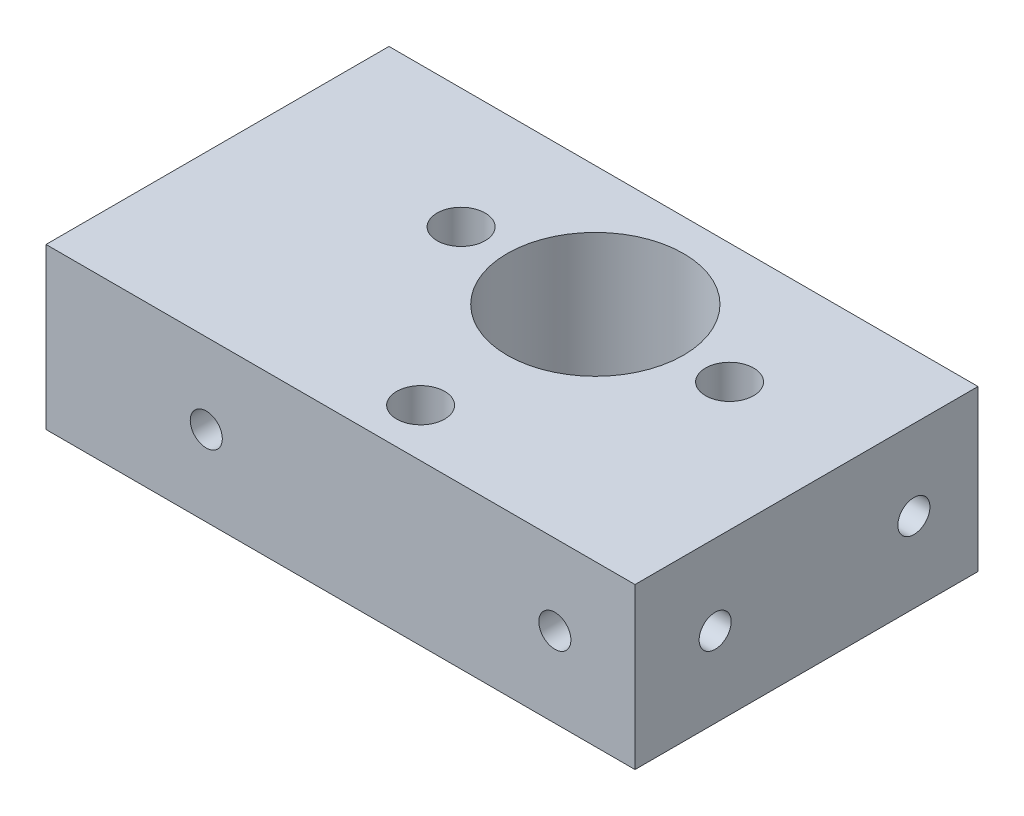
SolidWorks part; units mm, degrees
ref_plane "前视基准面" through (0, 0, 0) normal (0, 0, 1) x (1, 0, 0)
ref_plane "上视基准面" through (0, 0, 0) normal (0, 1, 0) x (1, 0, 0)
ref_plane "右视基准面" through (0, 0, 0) normal (1, 0, 0) x (0, 0, -1)
other "Configuration Table"
sketch "草图1" plane through (0, 0, 0) normal (0, 1, 0) x (1, 0, 0)
  line L0 (-8.375, 0) -> (8.375, 0)
  line L33 (-16.375, -7.5) -> (16.375, -7.5)
  line L34 (-16.375, -7.5) -> (-16.375, 7.5)
  line L35 (-16.375, 7.5) -> (16.375, 7.5)
  line L36 (16.375, -7.5) -> (16.375, 7.5)
  line L37 (-16.375, -7.5) -> (16.375, 7.5) construction
  line L38 (-16.375, 7.5) -> (16.375, -7.5) construction
  line L44 (16.375, -7.5) -> (-16.375, -7.5)
  line L45 (16.375, -7.5) -> (16.375, -13.9)
  line L46 (16.375, -13.9) -> (-16.375, -13.9)
  line L47 (-16.375, -7.5) -> (-16.375, -13.9)
  line L48 (-20.375, 7.5) -> (-16.375, 7.5)
  line L49 (-20.375, 7.5) -> (-20.375, -13.9)
  line L50 (-20.375, -13.9) -> (-16.375, -13.9)
  line L51 (-16.375, 7.5) -> (-16.375, -13.9)
  circle A0 centre (0, 0) radius 5.5
  circle A1 centre (-8.375, 0) radius 2.25
  circle A2 centre (-8.375, 0) radius 1.5
  circle A3 centre (8.375, 0) radius 2.25
  circle A4 centre (8.375, 0) radius 1.5
  circle A5 centre (0, -10.9) radius 1.5
  circle A6 centre (0, -10.9) radius 2.25
  point P0 (-90.6464, 22.0667)
  point P11 (0, 0)
  dimension "D1" = 11
  dimension "D2" = 15
  dimension "D3" = 16.75
  dimension "D4" = 3
  dimension "D5" = 4.5
  dimension "D6" = 8
  dimension "D7" = 13.9
  dimension "D8" = 4
extrude "凸台-拉伸1" add sketch "草图1" along normal blind 10 contours L33 L36 L35 L34 A3 A0 A1 | L33 L47 L46 L45 A6 | A4 A3 | A2 A1 | A6 A5 | L49 L50 L47 L34 L48 region at (-10.5614, 0, 0) region at (8.375, 0, -2.1864) region at (-16.0148, 0, 0) region at (-18.375, 0, 3.2) region at (0, 0, 7.8337) region at (-2.1864, 0, 10.9)
extrude "切除-拉伸1" cut sketch "草图1<16>" along direction (0, 1, 0) on the side of the normal offset from surface (7 mm away) 3 contours A1 | A6 | A3 up to face at (-2, 10, 3.2)
sketch "草图1<16>" plane through (0, 0, 0) normal (0, 1, 0) x (1, 0, 0) same geometry as "草图1"
sketch "草图2" plane through (0, 0, -7.5) normal (0, 0, -1) x (-1, 0, 0)
  circle A0 centre (-11.375, 5) radius 1
  circle A1 centre (10.375, 5) radius 1
  dimension "D1" = 2
extrude "切除-拉伸2" cut sketch "草图2" against normal blind 2
extrude "切除-拉伸3" cut sketch "草图2<2>" along normal blind 2 from surface starting at face at (-2, 5, 13.9)
sketch "草图2<2>" plane through (0, 0, -7.5) normal (0, 0, -1) x (-1, 0, 0) same geometry as "草图2"
sketch "草图3" plane through (16.375, 0, 0) normal (1, 0, 0) x (0, 0, -1)
  line L0 (-13.9, 10) -> (-13.9, 0) construction
  line L1 (7.5, 10) -> (7.5, 0) construction
  circle A0 centre (-8.9, 5) radius 1
  circle A1 centre (3.5, 5) radius 1
  point P4 (-13.9, 5)
  dimension "D1" = 2
  dimension "D2" = 5
  dimension "D3" = 4
extrude "切除-拉伸4" cut sketch "草图3" against normal blind 4 contours A0 | A1
